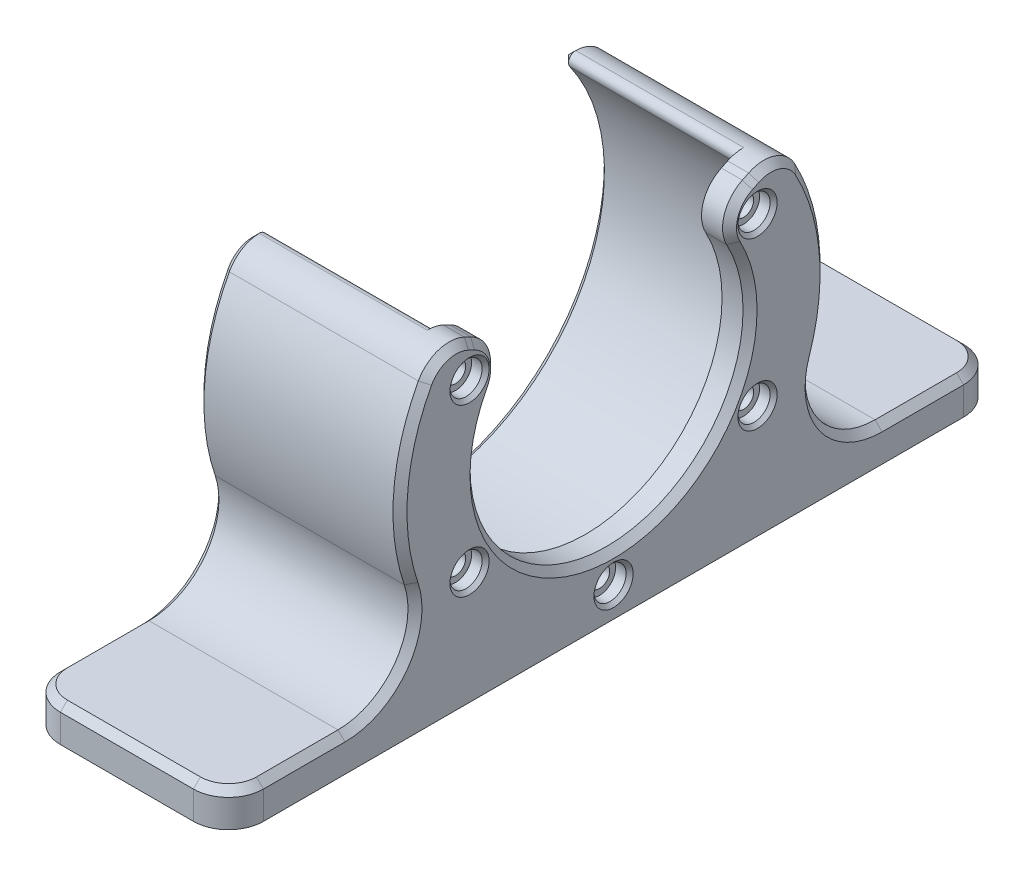
SolidWorks part; units mm, degrees
other "Markup1"
sketch "Sketch4" plane through (0, 45.0521, -55) normal (-0.3609, 0.4542, -0.8145) x (-0.9292, -0.2494, 0.2726)
ref_plane "Front Plane" through (0, 0, 0) normal (0, 0, 1) x (1, 0, 0)
ref_plane "Top Plane" through (0, 0, 0) normal (0, 1, 0) x (1, 0, 0)
ref_plane "Right Plane" through (0, 0, 0) normal (1, 0, 0) x (0, 0, -1)
sketch "Sketch1" plane through (0, 0, 0) normal (1, 0, 0) x (0, 0, -1)
  line L0 (55, 0) -> (-55, 0)
  line L1 (-55, 0) -> (-55, 5)
  line L2 (-55, 5) -> (-20.0312, 5)
  line L3 (0, -4.7055) -> (0, 45.6395) construction
  line L4 (-24.2712, 46.4705) -> (-14.0368, 41.5358)
  line L5 (0, 28) -> (-20.5681, 16.125) construction
  line L6 (0, 28) -> (20.5681, 16.125) construction
  line L7 (24.2712, 46.4705) -> (14.0368, 41.5358)
  line L8 (55, 5) -> (20.0312, 5)
  line L9 (55, 0) -> (55, 5)
  line L10 (0, 28) -> (-20.5681, 39.875) construction
  arc A0 (-14.0368, 41.5358) -> (14.0368, 41.5358) centre (0, 28) ccw
  arc A1 (-24.2712, 46.4705) -> (-20.0312, 5) centre (0, 28) ccw
  circle A2 centre (0, 28) radius 23.75 construction
  circle A3 centre (-20.5681, 16.125) radius 1.45
  circle A4 centre (20.5681, 16.125) radius 1.45
  arc A5 (24.2712, 46.4705) -> (20.0312, 5) centre (0, 28) cw
  circle A6 centre (0, 4.25) radius 1.45
  circle A7 centre (-20.5681, 39.875) radius 1.45
  circle A8 centre (20.5681, 39.875) radius 1.45
  point P20 (0, 0)
  dimension "D1" = 19.5
  dimension "D2" = 30.5
  dimension "D6" = 47.5
  dimension "D7" = 2.9
  dimension "D3" = 5
  dimension "D4" = 55
  dimension "D5" = 28
  dimension "D8" = 120
  dimension "D9" = 60
extrude "Boss-Extrude1" add sketch "Sketch1" along normal blind 29
fillet "Fillet1" radius 10 2 edges at (14.5, 5, 20.0312) (14.5, 5, -20.0312)
fillet "Fillet2" radius 5 4 edges at (14.5, 46.4705, -24.2712) (14.5, 41.5358, -14.0368) (14.5, 46.4705, 24.2712) (14.5, 41.5358, 14.0368)
sketch "Sketch2" plane through (0, 0, 0) normal (1, 0, 0) x (0, 0, -1)
  circle A0 centre (0, 28) radius 26.7
  dimension "D1" = 53.4
extrude "Cut-Extrude1" cut sketch "Sketch2" along normal blind 25
fillet "Fillet3" radius 1 2 edges at (12.5, 44.759, 20.7852) (12.5, 44.759, -20.7852)
fillet "Fillet4" radius 5 4 edges at (0, 2.5, -55) (0, 2.5, 55) (29, 2.5, -55) (29, 2.5, 55)
sketch "Sketch3" plane through (29, 0, 0) normal (1, 0, 0) x (0, 0, -1)
  circle A0 centre (-20.5681, 39.875) radius 2.3
  circle A1 centre (-20.5681, 16.125) radius 2.3
  circle A2 centre (0, 4.25) radius 2.3
  circle A3 centre (20.5681, 16.125) radius 2.3
  circle A4 centre (20.5681, 39.875) radius 2.3
  dimension "D1" = 4.6
extrude "Cut-Extrude2" cut sketch "Sketch3" against normal blind 2
chamfer "Chamfer1" distance 1 angle 45 30 edges at (1.4645, 5, 53.5355) (0, 5, 44.1784) (14.5, 5, 55) (0, 9.1733, 30.2298) (27.5355, 5, 53.5355) (0, 30.5211, 30.3956) (29, 5, 44.1784) (0, 44.309, 25.095) (29, 9.1733, 30.2298) (0, 44.5208, 21.693) (29, 30.5211, 30.3956) (0, 1.3, 0) (29, 44.8067, 24.0194) (0, 44.5208, -21.693) (29, 44.3386, 19.8497) (0, 44.309, -25.095) (29, 41.1605, 16.8146) (0, 30.5211, -30.3956) (29, 8.5, 0) (0, 9.1733, -30.2298) (29, 41.1605, -16.8146) (0, 5, -44.1784) (29, 44.3386, -19.8497) (1.4645, 5, -53.5355) (29, 44.8067, -24.0194) (14.5, 5, -55) (29, 30.5211, -30.3956) (27.5355, 5, -53.5355) (29, 9.1733, -30.2298) (29, 5, -44.1784)
chamfer "Chamfer2" distance 0.5 angle 45 5 edges at (29, 39.875, 18.2681) (29, 16.125, 18.2681) (29, 4.25, -2.3) (29, 16.125, -22.8681) (29, 39.875, -22.8681)
